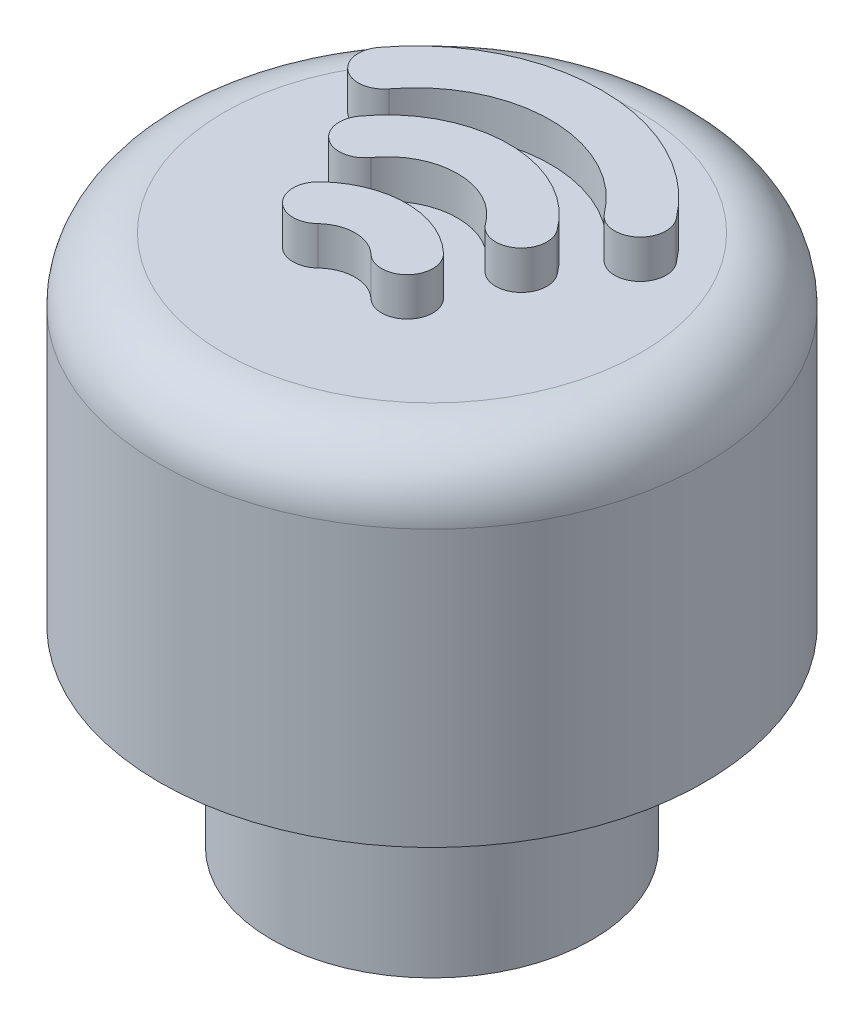
SolidWorks part; units mm, degrees
ref_plane "Front Plane" through (0, 0, 0) normal (0, 0, 1) x (1, 0, 0)
ref_plane "Top Plane" through (0, 0, 0) normal (0, 1, 0) x (1, 0, 0)
ref_plane "Right Plane" through (0, 0, 0) normal (1, 0, 0) x (0, 0, -1)
sketch "Sketch1" plane through (0, 0, 0) normal (0, 1, 0) x (1, 0, 0)
  circle A0 centre (0, 0) radius 4.25
  dimension "D1" = 8.5
extrude "Boss-Extrude1" add sketch "Sketch1" along normal blind 5.3 contours A0
sketch "Sketch2" plane through (0, 0, 0) normal (0, -1, 0) x (1, 0, 0)
  circle A0 centre (0, 0) radius 2.5
  dimension "D1" = 5
extrude "Boss-Extrude2" add sketch "Sketch2" along normal blind 3
shell "Shell2" thickness 0.7 removed face at (0, -3, -2.5)
fillet "Fillet1" radius 1 1 edges at (0, 5.3, 4.25) type face fillet first side face at (0, 5.3, 4.25) second side face at (0, 5.3, 4.25)
sketch "Sketch5" plane through (0, 5.3, 0) normal (0, 1, 0) x (1, 0, 0)
  point P0 (0, 0)
sketch "Sketch3" plane through (0, 5.3, 0) normal (0, 1, 0) x (1, 0, 0)
  line L1 (-3.2465, 0) -> (3.2465, 0) construction
  line L2 (0, 1.25) -> (0, 3.25) construction
  line L3 (0, 3.25) -> (0, -3.25) construction
  circle A0 centre (0, 0) radius 3.25 construction
  arc A1 (-0.6902, -1.0764) -> (0.6902, -1.0764) centre (0, -1.8) cw construction
  arc A2 (0.9663, -0.787) -> (-0.9663, -0.787) centre (0, -1.8) ccw
  arc A3 (0.4141, -1.3659) -> (-0.4141, -1.3659) centre (0, -1.8) ccw
  arc A4 (0.4141, -1.3659) -> (0.9663, -0.787) centre (0.6902, -1.0764) ccw
  arc A5 (-0.9663, -0.787) -> (-0.4141, -1.3659) centre (-0.6902, -1.0764) ccw
  arc A6 (-1.2198, 0.173) -> (1.2198, 0.173) centre (0, -0.7) cw construction
  arc A7 (1.5451, 0.4058) -> (-1.5451, 0.4058) centre (0, -0.7) ccw
  arc A8 (0.8945, -0.0598) -> (-0.8945, -0.0598) centre (0, -0.7) ccw
  arc A9 (0.8945, -0.0598) -> (1.5451, 0.4058) centre (1.2198, 0.173) ccw
  arc A10 (-1.5451, 0.4058) -> (-0.8945, -0.0598) centre (-1.2198, 0.173) ccw
  arc A11 (-2, 1.25) -> (2, 1.25) centre (0, -0.25) cw construction
  arc A12 (2.32, 1.49) -> (-2.32, 1.49) centre (0, -0.25) ccw
  arc A13 (1.68, 1.01) -> (-1.68, 1.01) centre (0, -0.25) ccw
  arc A14 (1.68, 1.01) -> (2.32, 1.49) centre (2, 1.25) ccw
  arc A15 (-2.32, 1.49) -> (-1.68, 1.01) centre (-2, 1.25) ccw
  point P5 (2.32, 1.49)
  point P12 (0, -0.8)
  point P20 (0, 0.8)
  point P25 (0.6875, 0.1503)
  point P29 (0, 2.25)
  point P35 (0, 1.85)
  point P36 (0, 0.4)
  point P37 (0, -1.2)
  point P38 (0, 0.1503)
  point P40 (-2.32, 1.49)
  point P41 (1.5451, 0.4058)
  point P42 (-1.5451, 0.4058)
  point P43 (-0.9663, -0.787)
  point P44 (0.9663, -0.787)
  point P45 (-1.5451, 0.4058)
  point P46 (1.4526, -0.1523)
  point P47 (-1.4526, -0.1523)
  point P48 (0.9797, -1.3525)
  point P49 (-0.9797, -1.3525)
  dimension "D1" = 1
  dimension "D2" = 1.5
  dimension "D3" = 2.5
  dimension "D8" = 0.8
  dimension "D9" = 0.8
  dimension "D10" = 0.8
  dimension "D4" = 4
  dimension "D5" = 1.6
  dimension "D11" = 1
  dimension "D12" = 0.8
extrude "Boss-Extrude4" add sketch "Sketch3" along normal blind 0.6
